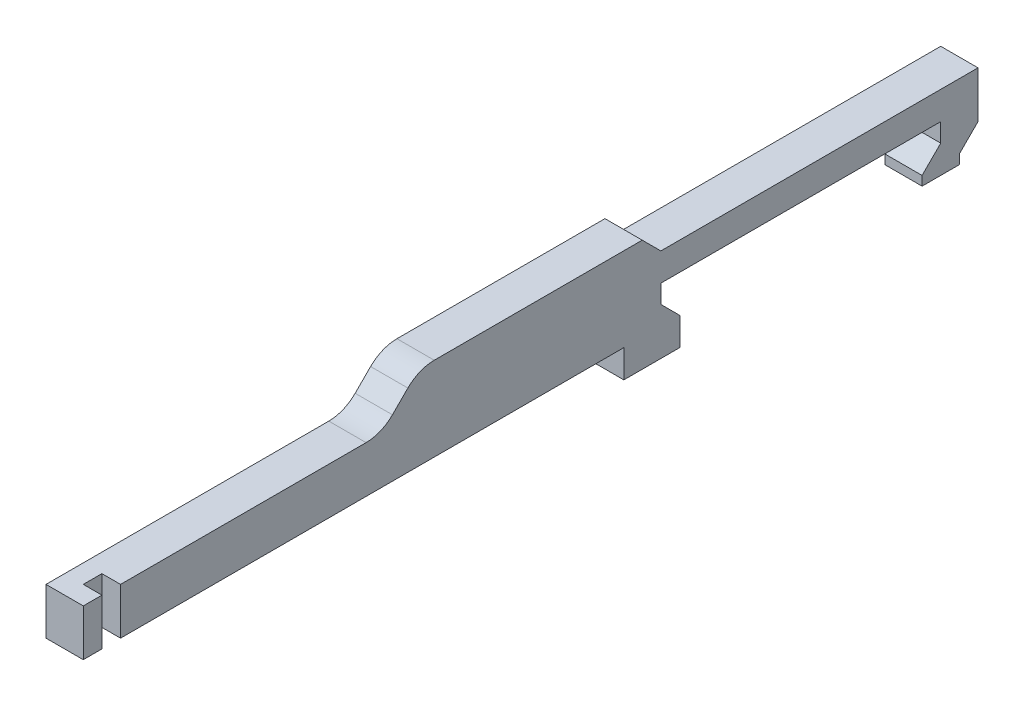
SolidWorks part; units mm, degrees
ref_plane "Спереди" through (0, 0, 0) normal (0, 0, 1) x (1, 0, 0)
ref_plane "Сверху" through (0, 0, 0) normal (0, 1, 0) x (1, 0, 0)
ref_plane "Справа" through (0, 0, 0) normal (1, 0, 0) x (0, 0, -1)
sketch "Эскиз1" plane through (0, 0, 0) normal (1, 0, 0) x (0, 0, -1)
  line L0 (16, 2.5) -> (18, 4.5)
  line L1 (0, 0) -> (16, 0)
  line L2 (0, 0) -> (0, 2.5)
  line L3 (0, 2.5) -> (16, 2.5)
  line L4 (16, 0) -> (16, 2.5)
  line L5 (18, 4.5) -> (18, 2.5) construction
  line L6 (18, 2.5) -> (16, 2.5) construction
  line L7 (18, 4.5) -> (29, 4.5)
  line L8 (16, 0) -> (29, 0)
  line L9 (29, 0) -> (29, -1.5)
  line L10 (29, -1.5) -> (32, -1.5)
  line L11 (32, -1.5) -> (32, 0)
  line L12 (32, 0) -> (31, 1)
  line L13 (31, 1) -> (31, 2)
  line L14 (31, 2) -> (46, 2)
  line L15 (32, 0) -> (31, 0) construction
  line L16 (31, 0) -> (31, 1) construction
  line L17 (38.5, 2) -> (38.5, 1) construction
  line L18 (45, 0) -> (46, 1)
  line L19 (46, 1) -> (46, 2)
  line L20 (45, 0) -> (45, -0.5)
  line L21 (45, -0.5) -> (47, -0.5)
  line L22 (47, -0.5) -> (47, 0)
  line L23 (47, 0) -> (48, 1)
  line L24 (48, 1) -> (48, 4.5)
  line L25 (48, 4.5) -> (29, 4.5)
  dimension "D1" = 2.5
  dimension "D2" = 16
  dimension "D3" = 2
  dimension "D4" = 2
  dimension "D5" = 11
  dimension "D6" = 13
  dimension "D7" = 1.5
  dimension "D8" = 3
  dimension "D9" = 1.5
  dimension "D10" = 1
  dimension "D11" = 1
  dimension "D12" = 1
  dimension "D13" = 15
  dimension "D14" = 0.5
  dimension "D15" = 2
extrude "Бобышка-Вытянуть1" add sketch "Эскиз1" along normal blind 2 contours L24 L25 L7 L0 L4 L8 L9 L10 L11 L12 L13 L14 L19 L18 L20 L21 L22 L23 | L1 L4 L3 L2 region at (0, 1.25, -8) region at (0, 2.3972, -30.6575)
fillet "Скругление1" radius 2 2 edges at (1, 4.5, -18) (1, 2.5, -16)
sketch "Эскиз2" plane through (0, 2.5, 0) normal (0, 1, 0) x (1, 0, 0)
  line L0 (2, 0) -> (2, 1) construction
  line L1 (2, 0) -> (2, 15.1716) construction
  line L3 (2, 1) -> (1, 1)
  line L4 (2, 1) -> (2, 2)
  line L5 (2, 2) -> (1, 2)
  line L6 (1, 1) -> (1, 2)
  dimension "D1" = 1
  dimension "D2" = 1
  dimension "D3" = 1
extrude "Вырез-Вытянуть1" cut sketch "Эскиз2" against normal through all
sketch "Эскиз3" plane through (2, 0, 0) normal (1, 0, 0) x (0, 0, -1)
  line L0 (48, 4.5) -> (48, 3.5)
  line L1 (48, 1) -> (48, 4.5) construction
  line L2 (48, 3.5) -> (30.9863, 3.5)
  line L3 (30.9863, 3.5) -> (29.9863, 4.5)
  line L4 (48, 4.5) -> (18.8284, 4.5) construction
  line L5 (29.9863, 4.5) -> (30.9863, 4.5)
  line L6 (30.9863, 4.5) -> (48, 4.5)
  line L7 (30.9863, 4.5) -> (30.9863, 3.5) construction
  dimension "D1" = 1
  dimension "D2" = 1
extrude "Вырез-Вытянуть2" cut sketch "Эскиз3" against normal through all
